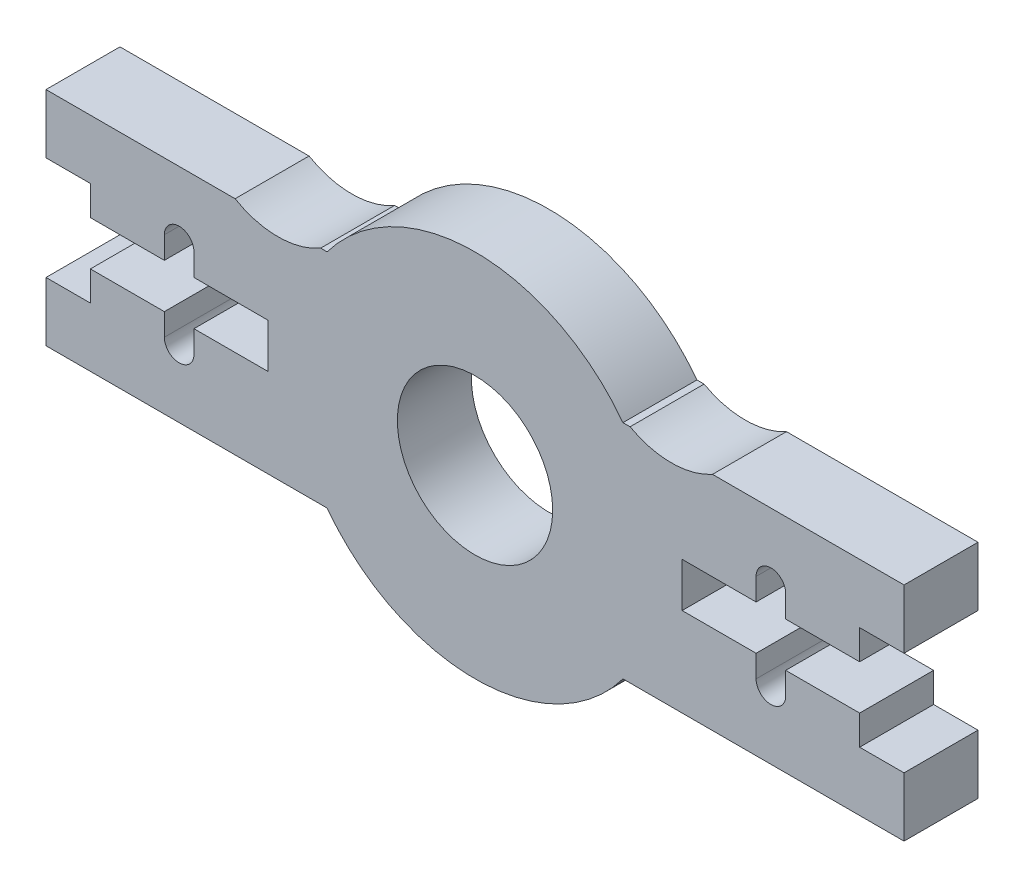
SolidWorks part; units mm, degrees
ref_plane "Front Plane" through (0, 0, 0) normal (0, 0, 1) x (1, 0, 0)
ref_plane "Top Plane" through (0, 0, 0) normal (0, 1, 0) x (1, 0, 0)
ref_plane "Right Plane" through (0, 0, 0) normal (1, 0, 0) x (0, 0, -1)
sketch "Sketch1" plane through (0, 0, 0) normal (0, 0, 1) x (1, 0, 0)
  line L0 (-20, 3) -> (-20, -3) construction
  line L1 (26, -7.5) -> (-26, -7.5)
  line L2 (26, -7.5) -> (26, 7.5)
  line L3 (26, 7.5) -> (-26, 7.5)
  line L4 (-26, -7.5) -> (-26, 7.5)
  line L5 (26, -7.5) -> (-26, 7.5) construction
  line L6 (26, 7.5) -> (-26, -7.5) construction
  line L7 (-14, -1.5) -> (-26, -1.5)
  line L8 (-14, -1.5) -> (-14, 1.5)
  line L9 (-14, 1.5) -> (-26, 1.5)
  line L10 (-26, -1.5) -> (-26, 1.5)
  line L11 (-14, -1.5) -> (-26, 1.5) construction
  line L12 (-14, 1.5) -> (-26, -1.5) construction
  line L13 (-19, 3) -> (-19, -3)
  line L14 (-21, 3) -> (-21, -3)
  line L15 (0, 7.5) -> (0, -7.5) construction
  line L16 (20, 3) -> (20, -3) construction
  line L17 (19, 3) -> (19, -3)
  line L18 (21, 3) -> (21, -3)
  line L19 (14, 1.5) -> (26, -1.5) construction
  line L20 (14, -1.5) -> (26, 1.5) construction
  line L21 (14, 1.5) -> (26, 1.5)
  line L22 (14, -1.5) -> (14, 1.5)
  line L23 (14, -1.5) -> (26, -1.5)
  circle A0 centre (0, 0) radius 12.5
  arc A1 (-19, 3) -> (-21, 3) centre (-20, 3) ccw
  arc A2 (-21, -3) -> (-19, -3) centre (-20, -3) ccw
  arc A3 (19, 3) -> (21, 3) centre (20, 3) cw
  arc A4 (21, -3) -> (19, -3) centre (20, -3) cw
  point P7 (-20, 0)
  point P14 (-20, 0)
  point P23 (20, 0)
  dimension "D1" = 25
  dimension "D2" = 52
  dimension "D3" = 3
  dimension "D4" = 12
  dimension "D5" = 2
  dimension "D6" = 8
  dimension "D7" = 15
extrude "Boss-Extrude1" add sketch "Sketch1" along normal blind 5 contours L3 A0 L1 | L3 A0 | L1 A0 | A2 L14 L7 L4 L1 A0 L3 L9 A1 L13 L8 | L18 A4 L17 L23 L22 L21 A3 L2 L3 A0 L1 region at (18, -7.2807, 0) region at (0, -9.5388, 0) region at (0, 0, 0) region at (-18, -7.2807, 0) region at (0, 9.5388, 0)
sketch "Sketch2" plane through (0, 0, 5) normal (0, 0, 1) x (1, 0, 0)
  circle A0 centre (0, 0) radius 5.25
  dimension "D1" = 10.5
extrude "Cut-Extrude1" cut sketch "Sketch2" against normal blind 5
sketch "Sketch3" plane through (0, 0, 5) normal (0, 0, 1) x (1, 0, 0)
  line L0 (26, 1.5) -> (26, 7.5) construction
  line L1 (-26, 7.5) -> (26, 7.5)
  line L2 (-26, 7.5) -> (-26, 11.2805)
  line L3 (-16, 21.2805) -> (16, 21.2805)
  line L4 (26, 7.5) -> (26, 11.2805)
  line L5 (-13.3258, 12.4694) -> (13.2683, 12.5305) construction
  line L6 (-1013.3258, 18.2805) -> (48986.6742, 18.2805) construction
  circle A0 centre (-13.3258, 12.4694) radius 5.75
  circle A1 centre (13.2683, 12.5305) radius 5.75
  arc A2 (10, 7.5) -> (-10, 7.5) centre (0, 0) ccw construction
  arc A3 (16, 21.2805) -> (26, 11.2805) centre (16, 11.2805) cw
  arc A4 (-16, 21.2805) -> (-26, 11.2805) centre (-16, 11.2805) ccw
  line M2 (26, 7.5) -> (10, 7.5)
  arc M3 (10, 7.5) -> (-10, 7.5) centre (0, 0) ccw
  line M4 (-10, 7.5) -> (-26, 7.5)
  dimension "D1" = 11.5
  dimension "D3" = 10
  dimension "D2" = 3
extrude "Boss-Extrude2" [suppressed] add sketch "Sketch3" against normal blind 5 contours L3 A4 L2 A0 A1 L4 A3 M4 M3 M2 | A0 M4 M3 | A1 M3 M2
extrude "Cut-Extrude2" cut sketch "Sketch3<3>" against normal blind 10 contours A0 | A1
sketch "Sketch3<3>" plane through (0, 0, 5) normal (0, 0, 1) x (1, 0, 0) same geometry as "Sketch3"
sketch "Sketch4" plane through (0, 0, 5) normal (0, 0, 1) x (1, 0, 0)
  line L1 (-26, 3.5) -> (-29, 3.5)
  line L2 (-26, 3.5) -> (-26, 7.5)
  line L3 (-26, 7.5) -> (-29, 7.5)
  line L4 (-29, 3.5) -> (-29, 7.5)
  line L5 (-26, -7.5) -> (-29, -7.5)
  line L6 (-26, -7.5) -> (-26, -3.5)
  line L7 (-26, -3.5) -> (-29, -3.5)
  line L8 (-29, -7.5) -> (-29, -3.5)
  line L9 (-21, -1.5) -> (-26, -1.5) construction
  line L10 (-21, 1.5) -> (-26, 1.5) construction
  line L11 (-26, 1.5) -> (-26, 7.5) construction
  dimension "D1" = 3
  dimension "D2" = 2
  dimension "D3" = 2
extrude "Boss-Extrude3" add sketch "Sketch4" against normal blind 5
mirror "Mirror1" about plane through (0, 0, 0) normal (1, 0, 0) of "Boss-Extrude3"
